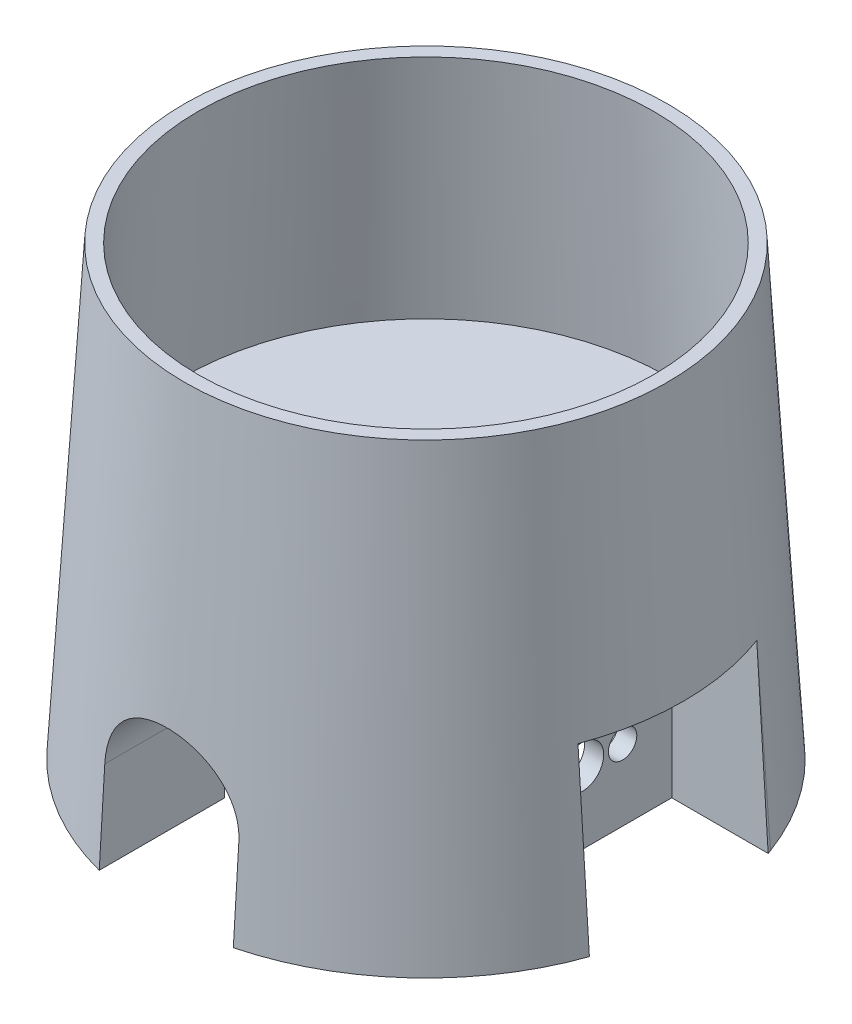
SolidWorks part; units mm, degrees
ref_plane "前视基准面" through (0, 0, 0) normal (0, 0, 1) x (1, 0, 0)
ref_plane "上视基准面" through (0, 0, 0) normal (0, 1, 0) x (1, 0, 0)
ref_plane "右视基准面" through (0, 0, 0) normal (1, 0, 0) x (0, 0, -1)
sketch "草图3" plane through (0, 0, 0) normal (1, 0, 0) x (0, 0, -1)
  line L0 (0, 0) -> (60, 0)
  line L1 (60, 0) -> (54, 100)
  line L2 (54, 100) -> (0, 100)
  line L3 (0, 100) -> (0, 0)
  dimension "D1" = 100
  dimension "D2" = 54
  dimension "D3" = 60
revolve "旋转2" add sketch "草图3" angle 360 about L3
sketch "草图5" plane through (0, 0, 0) normal (0, -1, 0) x (-1, 0, 0)
  line L0 (0, 0) -> (0, 71.9204) construction
  line L1 (0, 0) -> (72.7838, 0) construction
  line L3 (30.75, -30.1) -> (-30.75, -30.1)
  line L4 (30.75, -30.1) -> (30.75, 30.1)
  line L5 (30.75, 30.1) -> (-30.75, 30.1)
  line L6 (-30.75, -30.1) -> (-30.75, 30.1)
  dimension "D1" = 60.2
  dimension "D2" = 61.5
extrude "切除-拉伸1" cut sketch "草图5" against normal blind 40
sketch "草图6" plane through (0, 0, 0) normal (1, 0, 0) x (0, 0, -1)
  line L0 (0, 0) -> (0, 62.3248) construction
  line L1 (-60, 0) -> (60, 0) construction
  line L2 (-20, 0) -> (20, 0)
  line L3 (-20, 0) -> (-20, 40)
  line L4 (-20, 40) -> (20, 40)
  line L5 (20, 0) -> (20, 40)
  dimension "D1" = 40
  dimension "D2" = 40
extrude "切除-拉伸2" cut sketch "草图6" against normal blind 35 from offset 35 offset against normal yes
sketch "草图9" plane through (0, 0, 0) normal (1, 0, 0) x (0, 0, -1)
  line L0 (0, 0) -> (0, 62.3248) construction
  line L2 (-20, 0) -> (20, 0)
  line L3 (-20, 0) -> (-20, 40)
  line L4 (-20, 40) -> (20, 40)
  line L5 (20, 0) -> (20, 40)
  dimension "D1" = 40
  dimension "D2" = 40
extrude "切除-拉伸3" cut sketch "草图9" along normal blind 40 from offset 35
sketch "草图10" plane through (0, 0, 30.1) normal (0, 0, -1) x (-1, 0, 0)
  line L0 (0, 0) -> (0, 41.5034) construction
  line L1 (-15, 0) -> (-15, 20)
  line L2 (-56.5685, 0) -> (56.5685, 0) construction
  line L3 (-15, 0) -> (15, 0)
  line L4 (15, 0) -> (15, 20)
  arc A0 (-15, 20) -> (15, 20) centre (0, 20) cw
  dimension "D3" = 15
  dimension "D1" = 15
  dimension "D2" = 20
extrude "切除-拉伸4" cut sketch "草图10" against normal blind 40
sketch "草图11" plane through (0, 0, 0) normal (0, 0, 1) x (1, 0, 0)
  line L0 (-50.9946, 100) -> (-54.1746, 47)
  line L1 (54, 100) -> (-54, 100) construction
  line L2 (-54.1746, 47) -> (0, 47)
  line L3 (0, 47) -> (0, 100)
  line L4 (0, 100) -> (-50.9946, 100)
  line L5 (-54, 100) -> (-57.6, 40) construction
  dimension "D1" = 53
  dimension "D2" = 3
revolve "切除-旋转1" cut sketch "草图11" angle 360 about L3
hole_wizard "Ø2.5mm 暗销孔1" positions "草图14" profile "草图15" hole size "Ø2.5" standard "ISO" end condition through all
sketch "草图14" plane through (0, 47, 0) normal (0, 1, 0) x (1, 0, 0)
  line L0 (0, 0) -> (97.1322, 0) construction
  line L2 (0, 0) -> (0, -66.7943) construction
  point P17 (-10.5, 13.5)
  point P21 (-10.5, -13.5)
  point P22 (41.5, 13.5)
  point P32 (41.5, -13.5)
  dimension "D1" = 13.5
  dimension "D2" = 10.5
  dimension "D3" = 52
  dimension "D4" = 13.5
sketch "草图15" plane through (41.5, 47, 13.5) normal (1, 0, 0) x (0, 0, 1)
  line L0 (0, 0) -> (0, 47)
  line L1 (0, 47) -> (1.25, 47)
  line L2 (1.25, 47) -> (1.25, 0.025)
  line L3 (1.25, 0.025) -> (1.275, 0)
  line L5 (1.275, 0) -> (0, 0)
  line L6 (-1.25, 0.025) -> (-1.275, 0) construction
  line L11 (0, -6.35) -> (0, 107.95) construction
  dimension "通孔孔直径" = 2.5
  dimension "通孔孔深度" = 47
  dimension "近端锥形沉头孔直径" = 2.55
  dimension "近端锥形沉头孔角度" = 90
sketch "草图16" plane through (0, 0, -30.1) normal (0, 0, 1) x (1, 0, 0)
  line L0 (15, 20) -> (15, 0) construction
  line L1 (-15, 0) -> (-15, 20) construction
  line L2 (15, 20) -> (15, 0)
  line L3 (-15, 0) -> (-15, 20)
  line L4 (15, 0) -> (-15, 0)
  arc A0 (15, 20) -> (-15, 20) centre (0, 20) ccw construction
  arc A1 (15, 20) -> (-15, 20) centre (0, 20) ccw
extrude "切除-拉伸5" cut sketch "草图16" against normal blind 10
hole_wizard "3/8 (0.375) 直径孔1" positions "草图17" profile "草图18" hole size "3/8" standard "ANSI Inch" end condition through all
sketch "草图17" plane through (-35, 0, 0) normal (-1, 0, 0) x (0, 0, 1)
  point P0 (0, 16)
  dimension "D1" = 16
sketch "草图18" plane through (-35, 16, 0) normal (0, 1, 0) x (0, 0, 1)
  line L0 (0, 0) -> (0, 92.6)
  line L1 (0, 92.6) -> (4.7625, 92.6)
  line L2 (4.7625, 92.6) -> (4.7625, 0.635)
  line L3 (4.7625, 0.635) -> (5.3975, 0)
  line L5 (5.3975, 0) -> (0, 0)
  line L6 (-4.7625, 0.635) -> (-5.3975, 0) construction
  line L11 (0, -6.35) -> (0, 107.95) construction
  dimension "通孔孔直径" = 9.525
  dimension "通孔孔深度" = 92.6
  dimension "近端锥形沉头孔直径" = 10.795
  dimension "近端锥形沉头孔角度" = 90
hole_wizard "1/4 (0.25) 直径孔1" positions "草图19" profile "草图20" hole size "1/4" standard "ANSI Inch" end condition through all
sketch "草图19" plane through (-35, 0, 0) normal (-1, 0, 0) x (0, 0, 1)
  line L0 (0, 16) -> (0, 1.7388) construction
  line L2 (-0.701, 16) -> (-13.7276, 16) construction
  circle A0 centre (0, 16) radius 4.7625 construction
  point P15 (-9, 16)
  point P20 (9, 16)
  dimension "D1" = 9
sketch "草图20" plane through (-35, 16, 9) normal (0, 1, 0) x (0, 0, 1)
  line L0 (0, 0) -> (0, 92.6)
  line L1 (0, 92.6) -> (3.175, 92.6)
  line L2 (3.175, 92.6) -> (3.175, 0.635)
  line L3 (3.175, 0.635) -> (3.81, 0)
  line L5 (3.81, 0) -> (0, 0)
  line L6 (-3.175, 0.635) -> (-3.81, 0) construction
  line L11 (0, -6.35) -> (0, 107.95) construction
  dimension "通孔孔直径" = 6.35
  dimension "通孔孔深度" = 92.6
  dimension "近端锥形沉头孔直径" = 7.62
  dimension "近端锥形沉头孔角度" = 90
